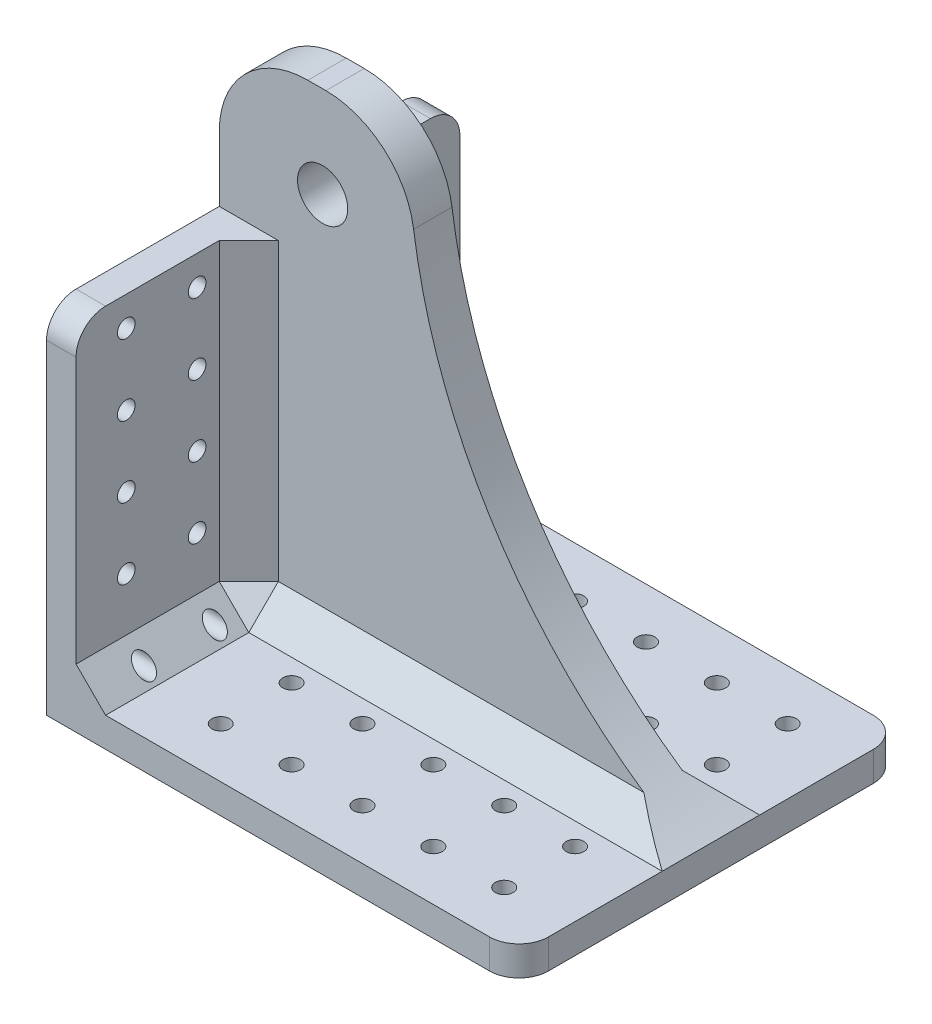
SolidWorks part; units mm, degrees
ref_plane "Front" through (0, 0, 0) normal (0, 0, 1) x (1, 0, 0)
ref_plane "Top" through (0, 0, 0) normal (0, 1, 0) x (1, 0, 0)
ref_plane "Right" through (0, 0, 0) normal (1, 0, 0) x (0, 0, -1)
sketch "Esquisse1" plane through (0, 0, 0) normal (0, 0, 1) x (1, 0, 0)
  line L0 (0, 0) -> (80, 0)
  line L1 (80, 0) -> (80, 5)
  line L2 (80, 5) -> (5, 5)
  line L3 (5, 5) -> (5, 60)
  line L4 (5, 60) -> (0, 60)
  line L5 (0, 60) -> (0, 0)
  dimension "D1" = 60
  dimension "D2" = 80
  dimension "D3" = 5
  dimension "D4" = 5
extrude "Boss.-Extru.1" add sketch "Esquisse1" along normal blind 65
sketch "Esquisse2" plane through (0, 5, 0) normal (0, 1, 0) x (1, 0, 0)
  line L0 (80, -32.5) -> (0, -32.5) construction
  line L1 (80, -65) -> (80, 0) construction
  line L3 (0, -35.75) -> (0, -29.25)
  line L5 (0, -29.25) -> (80, -29.25)
  line L6 (80, -29.25) -> (80, -35.75)
  line L7 (0, -35.75) -> (80, -35.75)
  line L8 (0, -65) -> (0, 0) construction
  dimension "D1" = 6.5
extrude "Boss.-Extru.2" add sketch "Esquisse2" along normal blind 81
sketch "Esquisse3" plane through (0, 0, 35.75) normal (0, 0, 1) x (1, 0, 0)
  line L0 (80, 86) -> (80, 5) construction
  line L1 (32, 86) -> (32, 107.0984) construction
  line L2 (0, 86) -> (80, 86) construction
  line L3 (32, 86) -> (80, 86)
  line L4 (80, 86) -> (80, 5)
  line L5 (0, 86) -> (0, 60) construction
  arc A0 (80, 5) -> (32, 86) centre (124.3437, 86) cw
  dimension "D1" = 32
extrude "Enlèv. mat.-Extru.1" cut sketch "Esquisse3" against normal through all both and the other way through all
fillet "Congé1" radius 15 2 edges at (0, 86, 32.5) (32, 86, 32.5)
sketch "Esquisse4" plane through (0, 0, 35.75) normal (0, 0, 1) x (1, 0, 0)
  line L0 (0, 60) -> (0, 0) construction
  line L1 (5, 60) -> (0, 60) construction
  circle A0 centre (17.5, 70.5) radius 4.25
  dimension "D2" = 10.5
  dimension "D3" = 8.5
  dimension "D1" = 17.5
extrude "Enlèv. mat.-Extru.2" cut sketch "Esquisse4" against normal through all both and the other way through all
chamfer "Chanfrein1" distance 5 angle 45 6 edges at (5, 5, 14.625) (42.5, 5, 29.25) (5, 32.5, 29.25) (5, 32.5, 35.75) (42.5, 5, 35.75) (5, 5, 50.375)
sketch "Esquisse5" plane through (0, 0, 0) normal (-1, 0, 0) x (0, 0, 1)
  line L0 (32.5, 0) -> (32.5, 62) construction
  line L1 (65, 0) -> (0, 0) construction
  line L3 (32.5, 31) -> (0, 31) construction
  line L5 (14.5, 31) -> (14.5, 55.0962) construction
  line L6 (8.5, 55) -> (8.5, 43) construction
  line L7 (8.5, 43) -> (8.5, 31) construction
  line L8 (20.5, 43) -> (20.5, 31) construction
  line L9 (20.5, 55) -> (20.5, 43) construction
  line L10 (20.5, 7) -> (20.5, 19) construction
  line L11 (8.5, 7) -> (8.5, 19) construction
  line L12 (56.5, 7) -> (56.5, 19) construction
  line L13 (44.5, 7) -> (44.5, 19) construction
  line L14 (44.5, 55) -> (44.5, 43) construction
  line L15 (44.5, 43) -> (44.5, 31) construction
  line L16 (56.5, 43) -> (56.5, 31) construction
  line L17 (56.5, 55) -> (56.5, 43) construction
  line L18 (50.5, 31) -> (50.5, 55.0962) construction
  line L19 (65, 60) -> (35.75, 60) construction
  circle A0 centre (8.5, 55) radius 1.5
  circle A1 centre (8.5, 43) radius 1.5
  circle A2 centre (8.5, 31) radius 1.5
  circle A3 centre (20.5, 31) radius 1.5
  circle A4 centre (20.5, 43) radius 1.5
  circle A5 centre (20.5, 55) radius 1.5
  circle A6 centre (20.5, 7) radius 1.5
  circle A7 centre (20.5, 19) radius 1.5
  circle A8 centre (8.5, 19) radius 1.5
  circle A9 centre (8.5, 7) radius 1.5
  circle A10 centre (56.5, 7) radius 1.5
  circle A11 centre (56.5, 19) radius 1.5
  circle A12 centre (44.5, 19) radius 1.5
  circle A13 centre (44.5, 7) radius 1.5
  circle A14 centre (44.5, 55) radius 1.5
  circle A15 centre (44.5, 43) radius 1.5
  circle A16 centre (44.5, 31) radius 1.5
  circle A17 centre (56.5, 31) radius 1.5
  circle A18 centre (56.5, 43) radius 1.5
  circle A19 centre (56.5, 55) radius 1.5
  dimension "D1" = 3
  dimension "D2" = 12
  dimension "D4" = 24
  dimension "D5" = 12
  dimension "D3" = 18
  dimension "D6" = 2
extrude "Enlèv. mat.-Extru.3" cut sketch "Esquisse5" against normal through all both and the other way through all
fillet "Congé2" radius 5 4 edges at (80, 2.5, 0) (80, 2.5, 65) (2.5, 60, 0) (2.5, 60, 65)
sketch "Esquisse6" plane through (0, 0, 0) normal (0, -1, 0) x (1, 0, 0)
  line L0 (0, 32.5) -> (90, 32.5) construction
  line L1 (0, 65) -> (0, 0) construction
  line L2 (45, 32.5) -> (45, 56.5) construction
  line L3 (45, 56.5) -> (57, 56.5) construction
  line L4 (57, 56.5) -> (57, 61.2046) construction
  line L5 (33, 56.5) -> (33, 61.2046) construction
  line L6 (45, 44.5) -> (60.4343, 44.5) construction
  line L7 (45, 50.5) -> (49.2932, 50.5) construction
  line L8 (45, 44.5) -> (57, 44.5) construction
  line L9 (45, 20.5) -> (57, 20.5) construction
  line L10 (45, 14.5) -> (49.2932, 14.5) construction
  line L11 (45, 20.5) -> (60.4343, 20.5) construction
  line L12 (45, 8.5) -> (57, 8.5) construction
  circle A0 centre (45, 56.5) radius 1.5
  circle A1 centre (57, 56.5) radius 1.5
  circle A2 centre (69, 56.5) radius 1.5
  circle A3 centre (21, 56.5) radius 1.5
  circle A4 centre (33, 56.5) radius 1.5
  circle A5 centre (33, 44.5) radius 1.5
  circle A6 centre (21, 44.5) radius 1.5
  circle A7 centre (69, 44.5) radius 1.5
  circle A8 centre (57, 44.5) radius 1.5
  circle A9 centre (45, 44.5) radius 1.5
  circle A10 centre (45, 20.5) radius 1.5
  circle A11 centre (57, 20.5) radius 1.5
  circle A12 centre (69, 20.5) radius 1.5
  circle A13 centre (21, 20.5) radius 1.5
  circle A14 centre (33, 20.5) radius 1.5
  circle A15 centre (33, 8.5) radius 1.5
  circle A16 centre (21, 8.5) radius 1.5
  circle A17 centre (69, 8.5) radius 1.5
  circle A18 centre (57, 8.5) radius 1.5
  circle A19 centre (45, 8.5) radius 1.5
  dimension "D1" = 3
  dimension "D2" = 12
  dimension "D4" = 12
  dimension "D5" = 90
extrude "Enlèv. mat.-Extru.4" cut sketch "Esquisse6" against normal through all both and the other way through all
